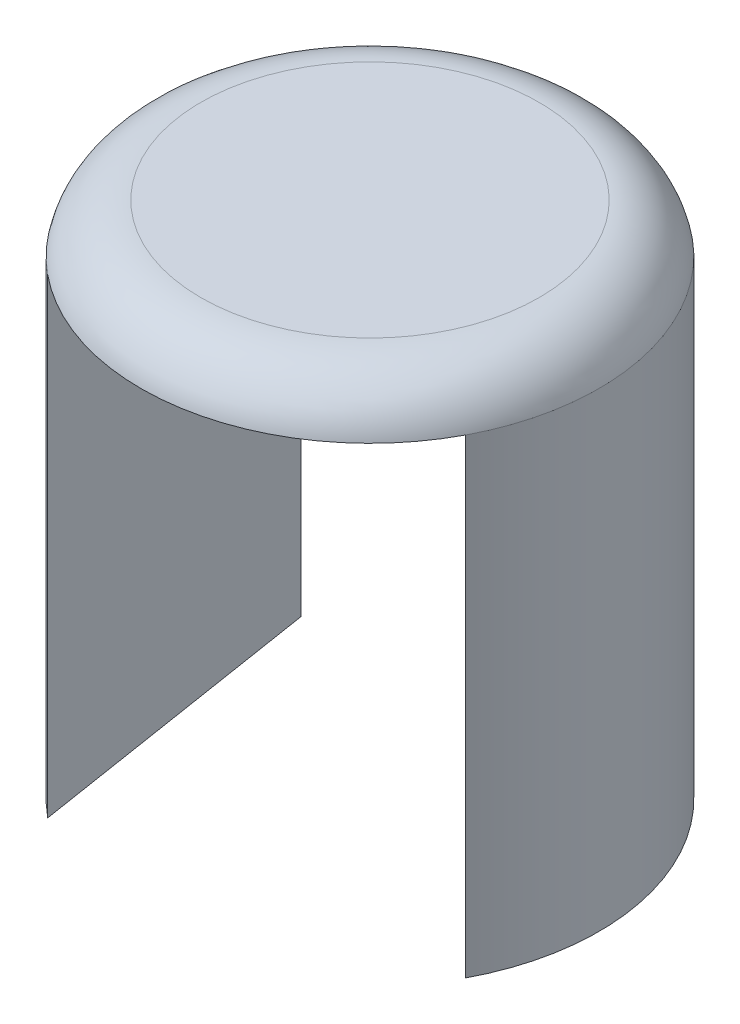
SolidWorks part; units mm, degrees
material "Aluminium 1050"
ref_plane "Front Plane" through (0, 0, 0) normal (0, 0, 1) x (1, 0, 0)
ref_plane "Top Plane" through (0, 0, 0) normal (0, 1, 0) x (1, 0, 0)
ref_plane "Right Plane" through (0, 0, 0) normal (1, 0, 0) x (0, 0, -1)
sketch "Sketch1" plane through (0, 0, 0) normal (0, 1, 0) x (1, 0, 0)
  circle A0 centre (0, 0) radius 37.5
  dimension "D1" = 75
extrude "Boss-Extrude1" add sketch "Sketch1" along normal blind 8 contours A0
fillet "Fillet1" radius 10 1 edges at (0, 8, 37.5)
sketch "Sketch3" plane through (0, 0, 0) normal (0, -1, 0) x (1, 0, 0)
  line L0 (0, 37.5) -> (0, -37.5)
  line L1 (26.1103, -26.9165) -> (33.1508, 17.5293)
  line L3 (-31.5579, -20.257) -> (-23.7524, 29.0185)
  line L4 (-23.7524, 29.0185) -> (-31.5579, -20.257) construction
  line L5 (33.1508, 17.5293) -> (26.1103, -26.9165) construction
  circle A0 centre (0, 0) radius 37.5 construction
  circle A1 centre (0, 0) radius 37.5
  circle M4 centre (0, 0) radius 37.5
  dimension "D1" = 75
extrude "Boss-Extrude3" add sketch "Sketch3" along normal up to surface (77 mm away) contours L3 M4 | L1 M4 region at (32.6206, 0, -5.1673) region at (-31.4524, 0, 4.9822)
